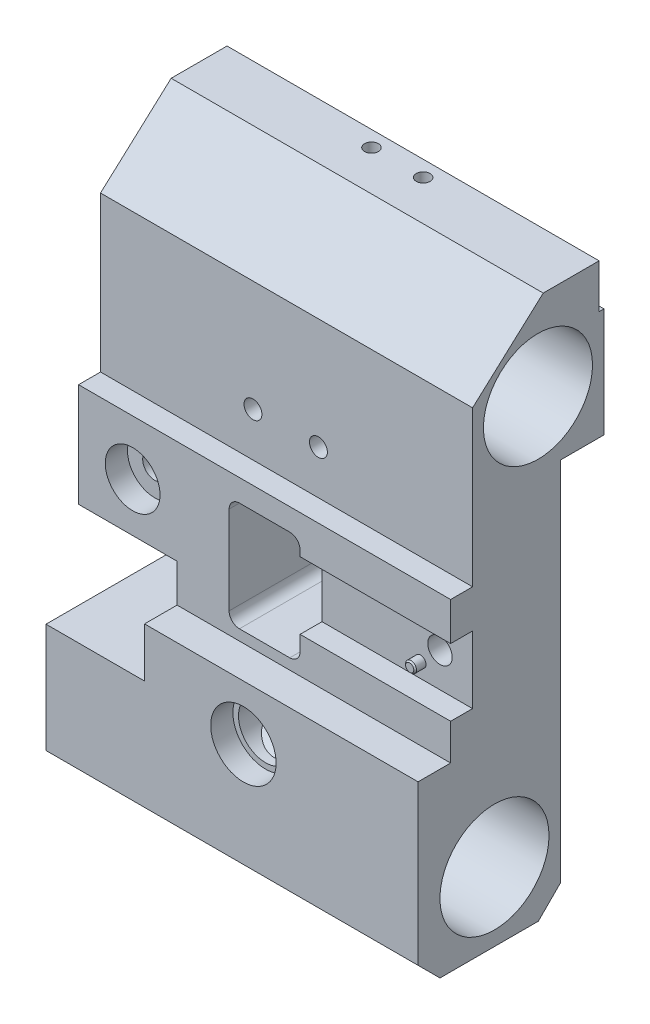
SolidWorks part; units mm, degrees
material "1060 Alloy"
ref_plane "Front Plane" through (0, 0, 0) normal (0, 0, 1) x (1, 0, 0)
ref_plane "Top Plane" through (0, 0, 0) normal (0, 1, 0) x (1, 0, 0)
ref_plane "Right Plane" through (0, 0, 0) normal (1, 0, 0) x (0, 0, -1)
sketch "Sketch1" plane through (0, 0, 0) normal (1, 0, 0) x (0, 0, -1)
  line L0 (14.15, 137.2) -> (30.37, 137.2)
  line L1 (30.37, 137.2) -> (30.37, 124.41)
  line L2 (30.37, 124.41) -> (31.79, 124.41)
  line L3 (31.79, 124.41) -> (31.79, 92.72)
  line L4 (31.79, 92.72) -> (19.1, 92.72)
  line L5 (19.1, 92.72) -> (19.1, -13.636)
  line L6 (19.1, -13.636) -> (12.736, -20)
  line L7 (12.736, -20) -> (-15.816, -20)
  line L8 (-15.816, -20) -> (-22.18, -13.636)
  line L9 (-22.18, -13.636) -> (-22.18, 32.5)
  line L10 (-22.18, 32.5) -> (-12.73, 32.5)
  line L11 (-12.73, 32.5) -> (-12.73, 73.61)
  line L12 (-12.73, 73.61) -> (-6.36, 73.61)
  line L13 (-6.36, 73.61) -> (-6.36, 118.61)
  line L14 (-6.36, 118.61) -> (14.15, 137.2)
  line L15 (-22.18, 32.5) -> (-22.18, 137.2) construction
  line L16 (-22.18, 137.2) -> (14.15, 137.2) construction
  line L17 (30.37, 137.2) -> (31.79, 137.2) construction
  line L18 (31.79, 137.2) -> (31.79, 124.41) construction
  line L19 (31.79, 92.72) -> (31.79, -20) construction
  line L20 (31.79, -20) -> (12.736, -20) construction
  line L21 (-22.18, -13.636) -> (-22.18, -20) construction
  line L22 (-22.18, -20) -> (-15.816, -20) construction
  line L23 (-22.18, 0) -> (31.79, 0) construction
  line L24 (0, -20) -> (0, 17.0401) construction
  line L25 (-22.18, -13.636) -> (19.1, -13.636) construction
  line L26 (0, -15.83) -> (46.0148, -15.83) construction
  line L27 (15.83, 0) -> (15.83, 26.825) construction
  line L28 (0, 15.83) -> (31.79, 15.83) construction
  line L29 (12.625, 111.985) -> (46.8932, 111.985) construction
  line L30 (12.625, 127.815) -> (56.5516, 127.815) construction
  line L31 (12.625, 96.155) -> (52.1782, 96.155) construction
  line L32 (30.37, 124.41) -> (30.37, 97.4751) construction
  line L33 (-15.83, 0) -> (-15.83, 21.2691) construction
  circle A0 centre (0, 0) radius 15.83
  circle A1 centre (12.625, 111.985) radius 15.83
  dimension "D19" = 111.985
  dimension "D14" = 31.66
  dimension "D1" = 41.28
  dimension "D2" = 38.15
  dimension "D3" = 157.2
  dimension "D4" = 44.48
  dimension "D5" = 1.42
  dimension "D6" = 31.69
  dimension "D7" = 25.46
  dimension "D8" = 31.83
  dimension "D9" = 52.5
  dimension "D10" = 93.61
  dimension "D11" = 9
  dimension "D12" = 12.625
  dimension "D13" = 16.22
  dimension "D15" = 45
  dimension "D16" = 3.27
  dimension "D17" = 6.35
  dimension "D18" = 4.17
extrude "Boss-Extrude1" add sketch "Sketch1" along normal blind 54 and the other way blind 54
sketch "Sketch2" plane through (0, 0, -19.1) normal (0, 0, -1) x (-1, 0, 0)
  line L0 (54, -13.636) -> (54, 92.72) construction
  line L1 (-7.3, 67.2) -> (7.3, 67.2)
  line L2 (-10.3, 64.2) -> (-10.3, 38.6)
  line L3 (-7.3, 35.6) -> (7.3, 35.6)
  line L4 (10.3, 64.2) -> (10.3, 38.6)
  line L5 (54, 43.53) -> (25.4, 43.53)
  line L6 (54, 43.53) -> (54, 18.13)
  line L7 (54, 18.13) -> (25.4, 18.13)
  line L8 (25.4, 43.53) -> (25.4, 18.13)
  line L9 (-9.25, 86.37) -> (9.75, 86.37) construction
  line L10 (-10.3, 64.2) -> (-10.3, 67.2) construction
  line L11 (-10.3, 67.2) -> (-7.3, 67.2) construction
  line L12 (7.3, 67.2) -> (10.3, 67.2) construction
  line L13 (10.3, 67.2) -> (10.3, 64.2) construction
  line L14 (10.3, 38.6) -> (10.3, 35.6) construction
  line L15 (10.3, 35.6) -> (7.3, 35.6) construction
  line L16 (-7.3, 35.6) -> (-10.3, 35.6) construction
  line L17 (-10.3, 35.6) -> (-10.3, 38.6) construction
  line L18 (-54, -13.636) -> (-54, 92.72) construction
  line L19 (54, -20) -> (-54, -20) construction
  line L21 (54, 137.2) -> (-54, 137.2) construction
  line L22 (-3.3, 16.595) -> (-3.3, 92.72) construction
  line L25 (54, 92.72) -> (-54, 92.72) construction
  line L26 (9.75, 86.37) -> (9.75, 92.72) construction
  line L27 (-9.25, 86.37) -> (-9.25, 92.72) construction
  line L28 (38.3, 57.72) -> (38.3, 92.72) construction
  line L29 (-44.55, 52.92) -> (-44.55, 92.72) construction
  circle A0 centre (-3.3, 16.595) radius 7.875
  circle A1 centre (-44.55, 52.92) radius 5.5 construction
  circle A2 centre (38.3, 57.72) radius 5.55 construction
  circle A3 centre (-9.25, 86.37) radius 2.6
  circle A4 centre (9.75, 86.37) radius 2.6
  circle A5 centre (-3.3, 16.595) radius 9.42 construction
  circle A6 centre (-9.25, 86.37) radius 4.425 construction
  circle A7 centre (9.75, 86.37) radius 4.425 construction
  circle A8 centre (38.3, 57.72) radius 3.525
  circle A9 centre (-44.55, 52.92) radius 3.55
  arc A10 (-7.3, 35.6) -> (-10.3, 38.6) centre (-7.3, 38.6) cw
  arc A11 (7.3, 35.6) -> (10.3, 38.6) centre (7.3, 38.6) ccw
  arc A12 (7.3, 67.2) -> (10.3, 64.2) centre (7.3, 64.2) cw
  arc A13 (-7.3, 67.2) -> (-10.3, 64.2) centre (-7.3, 64.2) ccw
  dimension "D1" = 3
  dimension "D17" = 18.84
  dimension "D18" = 15.75
  dimension "D20" = 8.85
  dimension "D21" = 5.2
  dimension "D22" = 7.05
  dimension "D23" = 11.1
  dimension "D24" = 7.1
  dimension "D25" = 11
  dimension "D2" = 43.7
  dimension "D3" = 43.7
  dimension "D4" = 55.6
  dimension "D5" = 70
  dimension "D6" = 38.13
  dimension "D7" = 25.4
  dimension "D8" = 28.6
  dimension "D9" = 15.7
  dimension "D10" = 44.25
  dimension "D11" = 63.25
  dimension "D12" = 9.45
  dimension "D13" = 50.7
  dimension "D14" = 35
  dimension "D15" = 6.35
  dimension "D16" = 39.8
  dimension "D19" = 76.125
extrude "Cut-Extrude1" cut sketch "Sketch2" against normal through all
sketch "Sketch3" plane through (0, 0, 12.73) normal (0, 0, 1) x (1, 0, 0)
  line L0 (54, 73.61) -> (54, 32.5) construction
  line L1 (54, 43) -> (10.3, 43)
  line L2 (54, 43) -> (54, 62.52)
  line L3 (54, 62.52) -> (10.3, 62.52)
  line L4 (10.3, 43) -> (10.3, 62.52)
  line L5 (10.3, 38.6) -> (10.3, 64.2) construction
  line L6 (-25.4, 32.5) -> (54, 32.5) construction
  dimension "D1" = 10.5
  dimension "D2" = 19.52
extrude "Cut-Extrude2" cut sketch "Sketch3" against normal blind 6.36
sketch "Sketch4" plane through (0, 0, 6.37) normal (0, 0, 1) x (1, 0, 0)
  line L0 (40.5, 47.335) -> (54, 47.335) construction
  line L2 (54, 43) -> (54, 62.52) construction
  line L3 (38.915, 48.92) -> (38.915, 62.52) construction
  line L4 (54, 62.52) -> (10.3, 62.52) construction
  circle A0 centre (38.915, 47.335) radius 1.585
  dimension "D1" = 3.17
  dimension "D2" = 13.5
  dimension "D3" = 13.6
extrude "Boss-Extrude2" add sketch "Sketch4" along normal blind 3.15
sketch "Sketch10" plane through (0, 0, -19.1) normal (0, 0, -1) x (-1, 0, 0)
  circle A1 centre (-38.915, 47.335) radius 1.585
  circle A2 centre (-38.915, 47.335) radius 1.585
  dimension "D1" = 0
extrude "Cut-Extrude6" cut sketch "Sketch10" against normal blind 20
sketch "Sketch11" plane through (0, 0, -19.1) normal (0, 0, -1) x (-1, 0, 0)
  circle A0 centre (38.3, 57.72) radius 5.5
  circle A1 centre (-44.55, 52.92) radius 5.42
  circle A2 centre (-9.25, 86.37) radius 4.55
  circle A3 centre (9.75, 86.37) radius 4.55
  circle M11 centre (38.3, 57.72) radius 3.525
  circle M12 centre (9.75, 86.37) radius 2.6
  circle M13 centre (-9.25, 86.37) radius 2.6
  dimension "D1" = 10.84
  dimension "D2" = 11
  dimension "D3" = 9.1
extrude "Cut-Extrude7" cut sketch "Sketch11" against normal blind 6.56 contours A0 M11 | A1 region at (-32.9556, 57.72, -19.1)
chamfer "Chamfer1" distance 0.4 angle 45 1 edges at (40.5, 47.335, 9.52)
sketch "Sketch5" plane through (0, 0, 12.73) normal (0, 0, 1) x (1, 0, 0)
  circle A0 centre (-38.3, 57.72) radius 7.945
  dimension "D1" = 15.89
extrude "Cut-Extrude3" cut sketch "Sketch5" against normal blind 6.44
sketch "Sketch6" plane through (0, 0, 22.18) normal (0, 0, 1) x (1, 0, 0)
  circle A0 centre (3.3, 16.595) radius 9.495
  dimension "D1" = 18.99
extrude "Cut-Extrude4" cut sketch "Sketch6" against normal blind 6.44
sketch "Sketch7" plane through (0, 0, -19.1) normal (0, 0, -1) x (-1, 0, 0)
  line L0 (25.4, 43.53) -> (25.4, 18.13) construction
  line L1 (25.4, 34.07) -> (16.63, 34.07)
  line L2 (25.4, 34.07) -> (25.4, -0.89)
  line L3 (25.4, -0.89) -> (16.63, -0.89)
  line L4 (16.63, 34.07) -> (16.63, -0.89)
  line L5 (54, 92.72) -> (-54, 92.72) construction
  dimension "D1" = 8.77
  dimension "D2" = 34.96
  dimension "D3" = 58.65
extrude "Boss-Extrude3" add sketch "Sketch7" along normal blind 3.1
sketch "Sketch8" plane through (0, 0, -22.2) normal (0, 0, -1) x (-1, 0, 0)
  line L0 (21.4, 3.82) -> (21.4, 92.72) construction
  line L1 (54, 92.72) -> (-54, 92.72) construction
  line L2 (16.63, -0.89) -> (25.4, -0.89) construction
  line L5 (25.4, -0.89) -> (25.4, 34.07) construction
  circle A0 centre (21.4, 29.135) radius 2
  circle A1 centre (21.4, 3.82) radius 2
  dimension "D2" = 4
  dimension "D1" = 4
  dimension "D3" = 4.71
  dimension "D4" = 30.025
extrude "Cut-Extrude5" cut sketch "Sketch8" against normal blind 15
extrude "Cut-Extrude8" cut sketch "Sketch11<3>" against normal blind 5.45 contours A2 M13 | A3 M12 region at (13.6713, 86.37, -19.1) region at (-5.3287, 86.37, -19.1)
sketch "Sketch11<3>" plane through (0, 0, -19.1) normal (0, 0, -1) x (-1, 0, 0) same geometry as "Sketch11"
sketch "Sketch12" plane through (0, 0, -19.1) normal (0, 0, -1) x (-1, 0, 0)
  circle A0 centre (-3.3, 16.595) radius 9.475
  dimension "D1" = 18.95
extrude "Cut-Extrude9" cut sketch "Sketch12" against normal blind 5.15
sketch "Sketch13" plane through (0, 0, -19.1) normal (0, 0, -1) x (-1, 0, 0)
  line L0 (-17.6348, 41.72) -> (20.3, 41.72) construction
  line L1 (-13.5, 41.72) -> (-13.5, 73.72) construction
  line L2 (13.2, 41.72) -> (13.2, 73.72) construction
  line L3 (-13.5, 73.72) -> (13.2, 73.72) construction
  line L4 (54, 92.72) -> (-54, 92.72) construction
  line L5 (-54, -13.636) -> (-54, 92.72) construction
  circle A0 centre (-13.5, 73.72) radius 2
  circle A1 centre (13.2, 73.72) radius 2
  circle A2 centre (-13.5, 41.72) radius 2
  circle A3 centre (13.2, 41.72) radius 2
  circle A4 centre (20.3, 41.72) radius 2
  circle A5 centre (-21, 41.92) radius 2
  circle A6 centre (21.4, 29.135) radius 2 construction
  dimension "D3" = 40.5
  dimension "D1" = 51
  dimension "D2" = 19
  dimension "D4" = 67.2
  dimension "D5" = 33
  dimension "D6" = 0.2
  dimension "D7" = 74.3
sketch "Sketch14" plane through (0, 0, -30.37) normal (0, 0, -1) x (-1, 0, 0)
  line L0 (-0.2, 130.91) -> (-0.2, 124.41) construction
  line L1 (54, 124.41) -> (-54, 124.41) construction
  line L2 (-0.2, 130.91) -> (-54, 130.91) construction
  line L3 (-54, 124.41) -> (-54, 137.2) construction
  circle A0 centre (-0.2, 130.91) radius 2
  circle A1 centre (13.2, 73.72) radius 2 construction
  dimension "D1" = 53.8
  dimension "D2" = 6.5
extrude "Cut-Extrude10" cut sketch "Sketch13" against normal blind 10
extrude "Cut-Extrude11" cut sketch "Sketch14" against normal blind 10
ref_axis "Axis1" through (-54, 111.985, -12.625) along (1, 0, 0)
ref_axis "Axis2" through (-54, 0, 0) along (1, 0, 0)
sketch "Sketch15" plane through (0, 137.2, 0) normal (0, 1, 0) x (-1, 0, 0)
  line L0 (0, -30.37) -> (0, -14.15) construction
  line L1 (54, -30.37) -> (-54, -30.37) construction
  line L2 (54, -14.15) -> (-54, -14.15) construction
  line L3 (-54, -30.37) -> (-54, -14.15) construction
  line L4 (54, -30.37) -> (54, -14.15) construction
  line L5 (12.7, -30.37) -> (12.7, -14.15) construction
  line L6 (-12.7, -30.37) -> (-12.7, -14.15) construction
  line L7 (54, -19.1) -> (-54, -19.1) construction
  line L8 (54, -19.1) -> (-54, -19.1) construction
  line L9 (54, -22.15) -> (-54, -22.15) construction
  line L10 (54, -12.625) -> (-54, -12.625) construction
  line L11 (54, -28.455) -> (54, 3.205) construction
  line L12 (54, -31.79) -> (-54, -31.79) construction
  line L13 (54, -31.79) -> (-54, -31.79) construction
  line L14 (7.5, -25.79) -> (-7.5, -25.79) construction
  line L15 (-54, -28.455) -> (54, -28.455) construction
  circle A0 centre (7.5, -25.79) radius 2
  circle A1 centre (-7.5, -25.79) radius 2
  dimension "D3" = 4
  dimension "D1" = 25.4
  dimension "D2" = 19.05
  dimension "D4" = 15
  dimension "D5" = 6
extrude "Cut-Extrude12" cut sketch "Sketch15" against normal up to surface (44.48 mm away) up to face at (0, 92.72, -25.445)
sketch "Sketch16" plane through (-25.4, 0, 0) normal (-1, 0, 0) x (0, 0, 1)
  line L0 (-8.6318, 32.3686) -> (7.5827, 28.5816) construction
  circle A0 centre (7.5827, 28.5816) radius 2
  circle A1 centre (-8.6318, 32.3686) radius 2
  dimension "D1" = 4
extrude "Cut-Extrude13" cut sketch "Sketch16" against normal blind 25
sketch "Sketch17" plane through (0, 0, -19.1) normal (0, 0, -1) x (-1, 0, 0)
  line L0 (-25.3804, 28.2306) -> (-44.7373, 28.2306) construction
  circle A0 centre (-44.7373, 28.2306) radius 2
  circle A1 centre (-25.3804, 28.2306) radius 2
  dimension "D1" = 4
extrude "Cut-Extrude14" cut sketch "Sketch17" against normal blind 25
